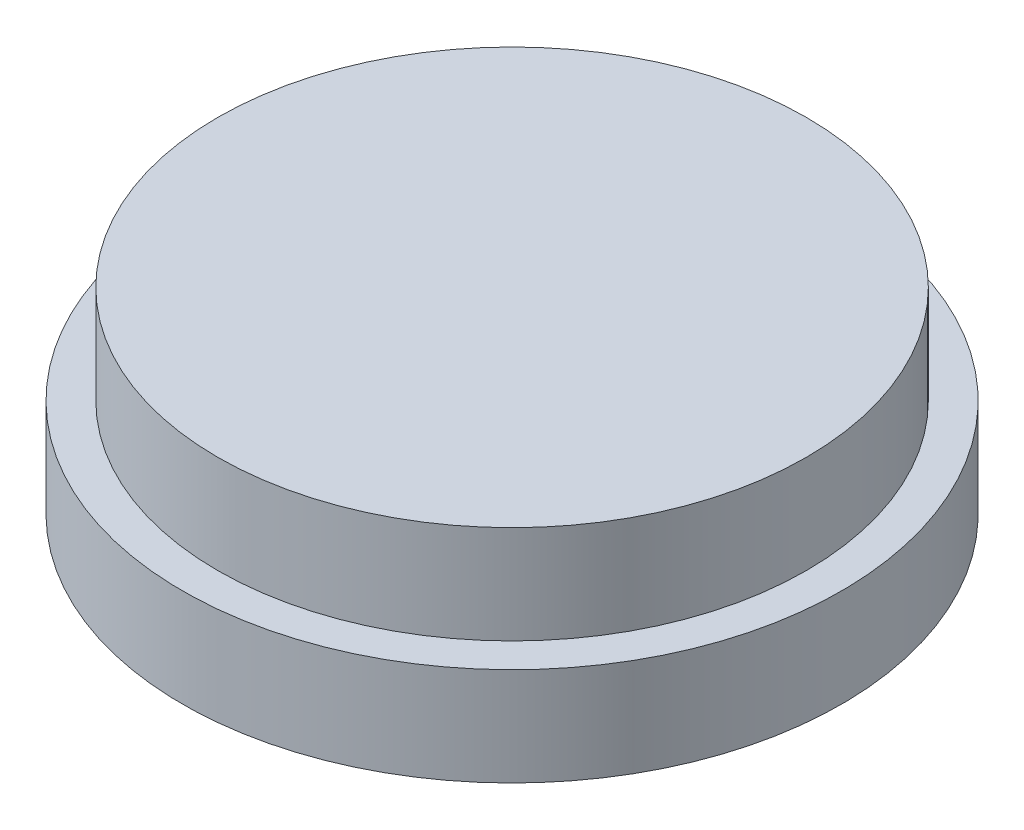
SolidWorks part; units mm, degrees
ref_plane "Ön Düzlem" through (0, 0, 0) normal (0, 0, 1) x (1, 0, 0)
ref_plane "Üst Düzlem" through (0, 0, 0) normal (0, 1, 0) x (1, 0, 0)
ref_plane "Sağ Düzlem" through (0, 0, 0) normal (1, 0, 0) x (0, 0, -1)
sketch "Sketch1" plane through (0, 0, 0) normal (0, 1, 0) x (1, 0, 0)
  circle A0 centre (0, 0) radius 30
  dimension "D1" = 60
extrude "Boss-Extrude1" add sketch "Sketch1" along normal blind 10 contours A0
sketch "Sketch2" plane through (0, 0, 0) normal (0, -1, 0) x (-1, 0, 0)
  circle A0 centre (0, 0) radius 27.5
  circle A1 centre (0, 0) radius 33.5885
  dimension "D1" = 55
extrude "Boss-Extrude2" add sketch "Sketch2" along normal blind 10
split "Split1" bodies to split 102 resulting bodies 103 104 split by face at (0, 0, -27.5)
sketch "Sketch3" plane through (0, 0, 0) normal (0, -1, 0) x (-1, 0, 0)
  circle A0 centre (0, 0) radius 21.9531
  circle A1 centre (0, 0) radius 76.981
